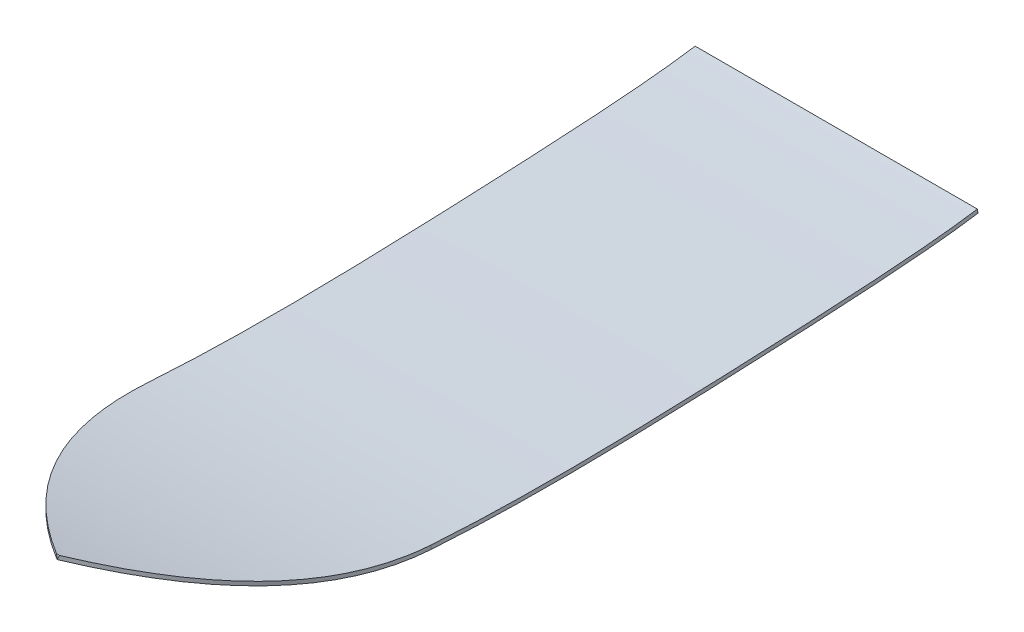
SolidWorks part; units mm, degrees
ref_plane "Front Plane" through (0, 0, 0) normal (0, 0, 1) x (1, 0, 0)
ref_plane "Top Plane" through (0, 0, 0) normal (0, 1, 0) x (1, 0, 0)
ref_plane "Right Plane" through (0, 0, 0) normal (1, 0, 0) x (0, 0, -1)
sketch "Sketch1" plane through (0, 0, 0) normal (1, 0, 0) x (0, 0, -1)
  line L20 (-2455.4698, 134.9826) -> (-2461.9469, 110.8362)
  line L21 (2508.0244, 12.0162) -> (2512.0431, -12.6587)
  spline S0 degree 3 poles (-2455.4698, 134.9826) (-2393.5382, 118.3699) (-2264.0772, 85.593) (-2101.6039, 49.4553) (-1969.5475, 23.0772) (-1839.1903, -1.0533) (-1680.1686, -27.1017) (-1497.2812, -52.3624) (-1308.6478, -74.074) (-1178.7542, -86.0213) (-1099.6701, -92.3771) (-1063.6682, -95.1931) (-1031.4384, -97.5596) (-954.7714, -102.8833) (-851.2507, -109.1851) (-704.536, -116.0261) (-560.5486, -120.8946) (-418.37, -124.0613) (-230.1742, -126.2974) (4.2222, -125.8049) (241.5717, -121.7799) (435.6236, -116.7956) (583.8946, -112.2437) (735.6055, -106.9397) (865.5648, -101.9378) (958.7687, -98.1518) (1012.7749, -95.9095) (1094.326, -92.4747) (1217.9524, -87.0792) (1383.8076, -79.2935) (1548.7608, -70.8533) (1764.8871, -58.6426) (1971.3229, -44.8694) (2254.3194, -21.4905) (2413.8411, -3.3232) (2508.0244, 12.0162) knots 0.002322 0.002322 0.002322 0.002322 0.03125 0.0625 0.078125 0.09375 0.125 0.15625 0.1875 0.226562 0.230469 0.234375 0.248047 0.25 0.28125 0.3125 0.34375 0.375 0.40625 0.46875 0.53125 0.5625 0.59375 0.625 0.65625 0.671875 0.679688 0.6875 0.71875 0.75 0.78125 0.8125 0.875 0.90625 1 1 1 1
  spline S1 degree 1 poles (-2461.9469, 110.8362) (2512.0431, -12.6587) knots 0 0 1 1 construction
  spline S2 degree 3 poles (-2461.9469, 110.8362) (-2428.4525, 101.8516) (-2361.2851, 84.3806) (-2260.3974, 59.7571) (-2159.7616, 36.7932) (-2026.4167, 8.4191) (-1862.2596, -22.7712) (-1671.7208, -53.6425) (-1489.2126, -78.5686) (-1344.4645, -95.0367) (-1233.1382, -106.0372) (-1151.8356, -113.2934) (-1072.7201, -119.6491) (-995.6565, -125.1948) (-919.8271, -130.055) (-820.2292, -135.6915) (-698.1098, -141.2998) (-554.2654, -146.0765) (-412.21, -149.1666) (-271.1761, -150.7798) (-130.4752, -151.0881) (10.4989, -150.2182) (152.3566, -148.2965) (295.695, -145.4108) (441.1109, -141.6494) (589.2496, -137.0801) (715.5547, -132.6501) (818.7127, -128.7595) (897.2422, -125.6742) (977.0535, -122.427) (1058.3256, -119.0245) (1140.2607, -115.4933) (1250.1388, -110.5995) (1388.1075, -104.1126) (1552.7616, -95.674) (1714.5686, -86.5176) (1871.5631, -76.5793) (1996.7192, -67.5927) (2092.4467, -59.9479) (2161.7936, -53.9783) (2228.4421, -47.7643) (2292.1476, -41.2975) (2342.5806, -35.6905) (2381.214, -31.0693) (2409.3029, -27.5342) (2436.4762, -23.9285) (2458.3336, -20.8637) (2475.3324, -18.375) (2487.8361, -16.4895) (2498.0428, -14.9032) (2506.0914, -13.6229) (2510.0545, -12.9826) (2512.0431, -12.6587) knots 0.002322 0.002322 0.002322 0.002322 0.01791 0.033499 0.049088 0.064677 0.095854 0.127032 0.158209 0.189386 0.204975 0.220564 0.236153 0.251741 0.26733 0.282919 0.314096 0.345274 0.376451 0.407629 0.438806 0.469983 0.501161 0.532338 0.563516 0.594693 0.625871 0.641459 0.657048 0.672637 0.688226 0.703814 0.719403 0.75058 0.781758 0.812935 0.844113 0.87529 0.890879 0.906468 0.922056 0.937645 0.953234 0.961028 0.968823 0.976617 0.984411 0.988308 0.992206 0.996103 0.998051 1 1 1 1
  dimension "D1" = 25
extrude "Boss-Extrude1" add sketch "Sketch1" along normal blind 1524 and the other way blind 1524
sketch "Sketch3" plane through (0, 0, 0) normal (0, 1, 0) x (1, 0, 0)
  line L0 (-900, 2541.7662) -> (900, 2541.7662)
  line L1 (-900, 2541.7662) -> (-900, -975.7674)
  line L2 (900, 2541.7662) -> (900, -975.7674)
  line L3 (0, 2955.5244) -> (0, -2061.9995) construction
  line L4 (-2934.2017, 5372.0277) -> (2797.2556, 5372.0277)
  line L5 (-2934.2017, 5372.0277) -> (-2934.2017, -2631.2782)
  line L6 (-2934.2017, -2631.2782) -> (2797.2556, -2631.2782)
  line L7 (2797.2556, 5372.0277) -> (2797.2556, -2631.2782)
  line L8 (-94.9374, 0) -> (0, 0) construction
  line L9 (-1524, -2461.9469) -> (1524, -2461.9469) construction
  line L11 (-1524, 1954.9582) -> (1524, 1954.9582) construction
  spline S0 degree 2 poles (-900, -975.7674) (-900, -1850.406) (0, -2461.9469) knots 0 0 0 1 1 1
  spline S1 degree 2 poles (900, -975.7674) (900, -1850.406) (0, -2461.9469) knots 0 0 0 1 1 1
  point P13 (0, -2461.9469)
  dimension "D1" = 1800
extrude "Cut-Extrude1" cut sketch "Sketch3" against normal through all both and the other way through all
